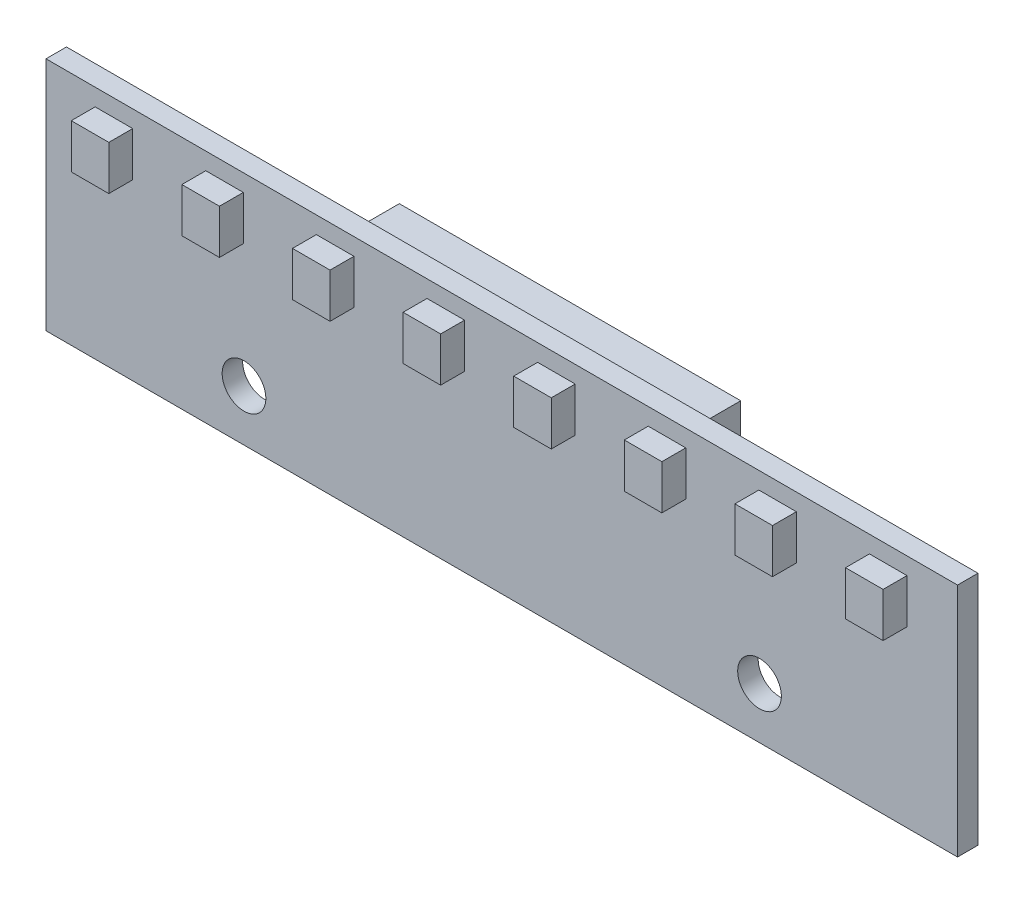
SolidWorks part; units mm, degrees
ref_plane "Front Plane" through (0, 0, 0) normal (0, 0, 1) x (1, 0, 0)
ref_plane "Top Plane" through (0, 0, 0) normal (0, 1, 0) x (1, 0, 0)
ref_plane "Right Plane" through (0, 0, 0) normal (1, 0, 0) x (0, 0, -1)
sketch "Sketch1" plane through (0, 0, 0) normal (0, 0, 1) x (1, 0, 0)
  line L1 (0, 0) -> (66.75, 0)
  line L2 (0, 0) -> (0, 17.25)
  line L3 (0, 17.25) -> (66.75, 17.25)
  line L4 (66.75, 0) -> (66.75, 17.25)
  dimension "D1" = 66.75
  dimension "D2" = 17.25
extrude "Boss-Extrude1" add sketch "Sketch1" along normal blind 1.5
sketch "Sketch2" plane through (0, 0, 1.5) normal (0, 0, 1) x (1, 0, 0)
  line L0 (0, 17.25) -> (0, 0) construction
  line L1 (3.6, 16) -> (6.35, 16)
  line L2 (3.6, 16) -> (3.6, 12.75)
  line L3 (3.6, 12.75) -> (6.35, 12.75)
  line L4 (6.35, 16) -> (6.35, 12.75)
  line L5 (66.75, 17.25) -> (0, 17.25) construction
  dimension "D1" = 3.25
  dimension "D2" = 2.75
  dimension "D3" = 3.6
  dimension "D4" = 1.25
extrude "Boss-Extrude2" add sketch "Sketch2" along normal blind 1.75
pattern_linear "LPattern1" count 8 spacing 8.1 along (1, 0, 0) of "Boss-Extrude2"
ref_axis "Axis1" through (33.375, 17.25, 0) along (0, -0.9962, 0.0866)
sketch "Sketch3" plane through (0, 0, 1.5) normal (0, 0, 1) x (1, 0, 0)
  line L1 (0, 0) -> (66.75, 0) construction
  line L2 (0, 17.25) -> (0, 0) construction
  circle A0 centre (14.5, 3.75) radius 1.6
  dimension "D1" = 3.2
  dimension "D2" = 3.75
  dimension "D3" = 14.5
extrude "Cut-Extrude1" cut sketch "Sketch3" against normal through all
ref_plane "Plane1" through (33.375, 0, 0) normal (-1, 0, 0) x (0, 0, 1)
mirror "Mirror1" about plane through (33.375, 0, 0) normal (-1, 0, 0) of "Cut-Extrude1"
sketch "Sketch4" plane through (0, 0, 0) normal (0, 0, -1) x (-1, 0, 0)
  line L0 (0, 0) -> (-66.75, 0) construction
  line L1 (-45.875, 0) -> (-20.875, 0)
  line L2 (-45.875, 0) -> (-45.875, 16)
  line L3 (-45.875, 16) -> (-20.875, 16)
  line L4 (-20.875, 0) -> (-20.875, 16)
  line L7 (-33.375, -0.825) -> (-33.375, 0.825) construction
  dimension "D1" = 25
  dimension "D2" = 16
  dimension "D3" = 12.5
extrude "Boss-Extrude3" add sketch "Sketch4" along normal blind 3.5
ref_axis "Axis2" through (3.6, 14.375, 3.25) along (1, 0, 0)
